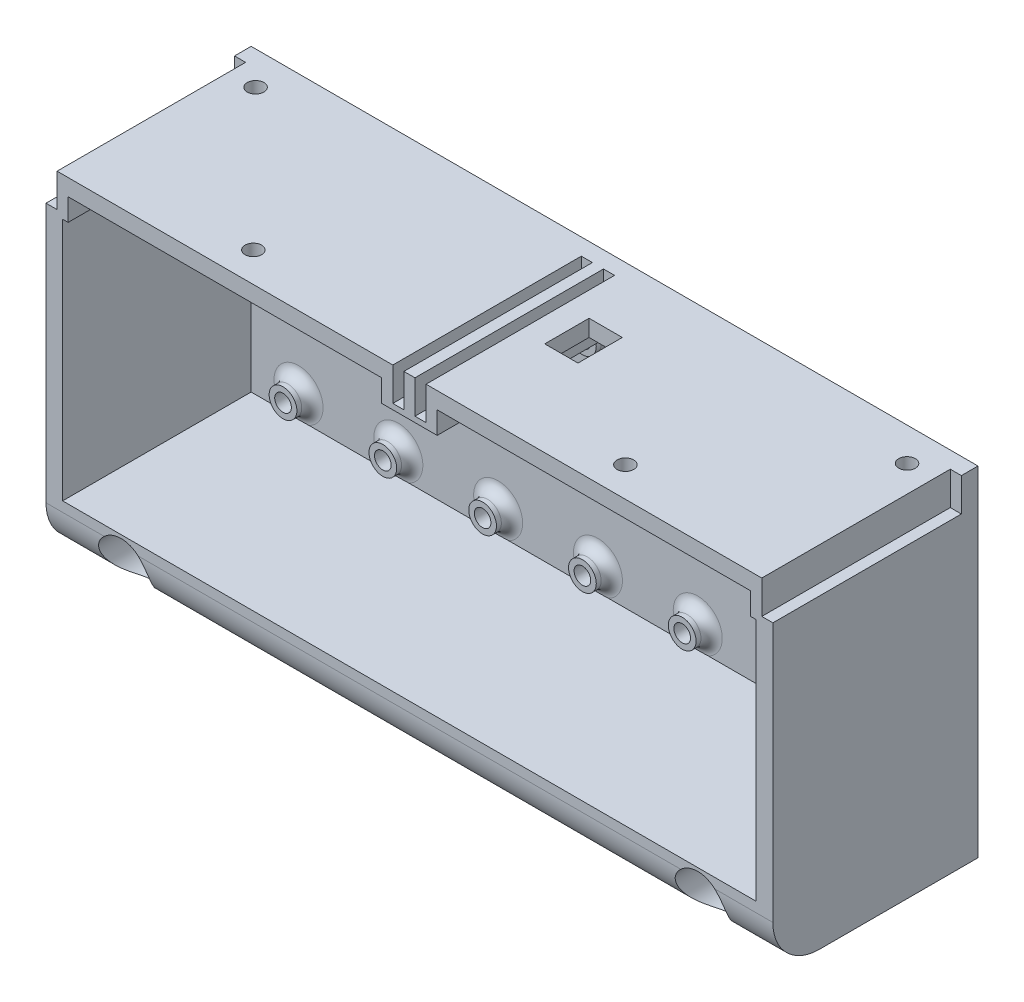
SolidWorks part; units mm, degrees
material "ABS"
ref_plane "Alzado" through (0, 0, 0) normal (0, 0, 1) x (1, 0, 0)
ref_plane "Planta" through (0, 0, 0) normal (0, 1, 0) x (1, 0, 0)
ref_plane "Vista lateral" through (0, 0, 0) normal (1, 0, 0) x (0, 0, -1)
sketch "Croquis2" plane through (0, 0, 0) normal (0, 0, 1) x (1, 0, 0)
  line L0 (0, 0) -> (131.1, 0)
  line L1 (131.1, 0) -> (131.1, -54)
  line L2 (131.1, -54) -> (0, -54)
  line L3 (0, -54) -> (0, 0)
  dimension "D1" = 131.1
  dimension "D2" = 54
extrude "Saliente-Extruir2" add sketch "Croquis2" along normal blind 3
sketch "Croquis3" plane through (0, 0, 3) normal (0, 0, 1) x (1, 0, 0)
  line L0 (0, -6) -> (2, -6)
  line L1 (0, 0) -> (0, -54) construction
  line L2 (2, -6) -> (2, 0)
  line L3 (131.1, 0) -> (0, 0) construction
  line L4 (2, 0) -> (129.1, 0)
  line L5 (129.1, 0) -> (129.1, -6)
  line L6 (129.1, -6) -> (131.1, -6)
  line L7 (131.1, -54) -> (131.1, 0) construction
  line L8 (131.1, -6) -> (131.1, -54)
  line L9 (131.1, -54) -> (0, -54)
  line L10 (0, -54) -> (0, -6)
  line L11 (65.55, 0) -> (66.55, 0)
  line L12 (65.55, 0) -> (64.55, 0)
  line L13 (64.55, 0) -> (64.55, -6)
  line L14 (66.55, 0) -> (66.55, -6)
  line L15 (64.55, -6) -> (62.55, -6)
  line L16 (62.55, -6) -> (62.55, 0)
  line L17 (66.55, -6) -> (68.55, -6)
  line L18 (68.55, -6) -> (68.55, 0)
  line L19 (3, -7) -> (128.1, -7)
  line L20 (128.1, -7) -> (128.1, -51)
  line L21 (128.1, -51) -> (3, -51)
  line L22 (3, -51) -> (3, -7)
  point P31 (130.1, -6)
  line M15 (0, 0) -> (0, -54)
  line M16 (0, -54) -> (131.1, -54)
  line M17 (131.1, -54) -> (131.1, 0)
  line M18 (131.1, 0) -> (0, 0)
  dimension "D1" = 2
  dimension "D2" = 2
  dimension "D3" = 6
  dimension "D4" = 2
  dimension "D5" = 2
  dimension "D6" = 1
  dimension "D7" = 1
  dimension "D8" = 3
  dimension "D9" = 3
  dimension "D10" = 3
  dimension "D11" = 1
extrude "Saliente-Extruir3" add sketch "Croquis3" along normal blind 34 contours L18 L17 L14 L4 L13 L15 L16 L2 L0 L6 L5 L21 L22 L19 L20 M18 M15 M16 M17 region at (1, -7.4179, 3)
sketch "Croquis4" plane through (0, -54, 0) normal (0, -1, 0) x (1, 0, 0)
  line L4 (0, 0) -> (131.1, 0)
  line L5 (131.1, 0) -> (131.1, 37)
  line L6 (131.1, 37) -> (0, 37)
  line L7 (0, 37) -> (0, 0)
  line L8 (0, 0) -> (131.1, 0)
  line L9 (131.1, 0) -> (131.1, 37)
  line L10 (131.1, 37) -> (0, 37)
  line L11 (0, 37) -> (0, 0)
  dimension "D1" = 0
extrude "Saliente-Extruir4" add sketch "Croquis4" along normal blind 7.2
sketch "Croquis5" plane through (0, 0, 37) normal (0, 0, 1) x (1, 0, 0)
  line L0 (3, -7) -> (128.1, -7) construction
  line L1 (4, -7) -> (60.55, -7)
  line L2 (4, -7) -> (4, -3)
  line L3 (4, -3) -> (60.55, -3)
  line L4 (60.55, -7) -> (60.55, -3)
  line L5 (62.55, 0) -> (2, 0) construction
  line L6 (65.55, -7) -> (65.55, 0) construction
  line L7 (66.55, 0) -> (64.55, 0) construction
  line L8 (127.1, -3) -> (70.55, -3)
  line L9 (70.55, -7) -> (70.55, -3)
  line L10 (127.1, -7) -> (70.55, -7)
  line L11 (127.1, -7) -> (127.1, -3)
  dimension "D1" = 1
  dimension "D2" = 2
  dimension "D3" = 3
extrude "Cortar-Extruir1" cut sketch "Croquis5" against normal up to vertex (34 mm away) up to point (3, -7, 3)
sketch "Croquis6" plane through (0, -3, 0) normal (0, -1, 0) x (1, 0, 0)
  line L0 (60.55, 37) -> (4, 37) construction
  line L1 (0, 37) -> (0, 3) construction
  line L2 (131.1, 37) -> (131.1, 3) construction
  line L3 (131.1, 0) -> (0, 0) construction
  line L4 (127.1, 3) -> (70.55, 3) construction
  line L5 (72.95, 20) -> (78.95, 20)
  line L6 (72.95, 20) -> (72.95, 12)
  line L7 (72.95, 12) -> (78.95, 12)
  line L8 (78.95, 20) -> (78.95, 12)
  circle A0 centre (32, 31.6) radius 1.5
  circle A1 centre (99.1, 31.6) radius 1.5
  circle A2 centre (6.8, 6) radius 1.5
  circle A3 centre (124.3, 6) radius 1.5
  point P16 (63.45, 31.6)
  dimension "D3" = 3
  dimension "D1" = 5.4
  dimension "D2" = 32
  dimension "D4" = 32
  dimension "D5" = 6.8
  dimension "D6" = 6
  dimension "D7" = 6.8
  dimension "D8" = 63.45
  dimension "D9" = 4.4
  dimension "D10" = 9
  dimension "D11" = 6
  dimension "D12" = 8
extrude "Cortar-Extruir2" cut sketch "Croquis6" against normal up to next
sketch "Croquis8" plane through (0, 0, 37) normal (0, 0, 1) x (1, 0, 0)
  line L0 (65.55, -61.2) -> (65.55, -51) construction
  line L1 (131.1, -61.2) -> (0, -61.2) construction
  line L2 (128.1, -51) -> (3, -51) construction
  circle A0 centre (13.55, -56.1) radius 4.5
  circle A1 centre (117.55, -56.1) radius 4.5
  point P8 (65.55, -56.1)
  dimension "D1" = 9
  dimension "D2" = 52
extrude "Cortar-Extruir3" cut sketch "Croquis8" against normal blind 33
sketch "Croquis9" plane through (0, 0, 37) normal (0, 0, 1) x (1, 0, 0)
  circle A0 centre (13.55, -56.1) radius 2.5
  circle A1 centre (117.55, -56.1) radius 2.5
  dimension "D1" = 5
extrude "Cortar-Extruir4" cut sketch "Croquis9" against normal through all
fillet "Redondeo1" radius 8.4 1 edges at (65.55, -61.2, 37)
sketch "Croquis10" plane through (0, 0, 3) normal (0, 0, 1) x (1, 0, 0)
  line L0 (60.55, -7) -> (70.55, -7) construction
  line L1 (60.55, -7) -> (70.55, -7) construction
  circle A0 centre (65.55, -10) radius 2.5
  circle A1 centre (65.55, -10) radius 1.5
  circle A2 centre (83.55, -10) radius 1.5
  circle A3 centre (83.55, -10) radius 2.5
  circle A4 centre (101.55, -10) radius 1.5
  circle A5 centre (101.55, -10) radius 2.5
  circle A6 centre (119.55, -10) radius 1.5
  circle A7 centre (119.55, -10) radius 2.5
  circle A8 centre (83.55, -47) radius 1.5
  circle A9 centre (83.55, -47) radius 2.5
  circle A10 centre (101.55, -47) radius 1.5
  circle A11 centre (101.55, -47) radius 2.5
  circle A12 centre (119.55, -47) radius 1.5
  circle A13 centre (119.55, -47) radius 2.5
  circle A16 centre (47.55, -10) radius 2.5
  circle A17 centre (47.55, -10) radius 1.5
  circle A18 centre (29.55, -10) radius 2.5
  circle A19 centre (29.55, -10) radius 1.5
  circle A20 centre (11.55, -10) radius 2.5
  circle A21 centre (11.55, -10) radius 1.5
  circle A22 centre (47.55, -47) radius 2.5
  circle A23 centre (47.55, -47) radius 1.5
  circle A24 centre (29.55, -47) radius 2.5
  circle A25 centre (29.55, -47) radius 1.5
  circle A26 centre (11.55, -47) radius 2.5
  circle A27 centre (11.55, -47) radius 1.5
  circle A28 centre (65.55, -47) radius 2.5
  circle A29 centre (65.55, -47) radius 1.5
  circle A30 centre (65.55, -47) radius 2.5 [skipped]
  circle A31 centre (65.55, -47) radius 1.5 [skipped]
  point P5 (65.55, -7)
  dimension "D1" = 5
  dimension "D3" = 3
  dimension "D2" = 3
  dimension "D4" = 4
  dimension "D5" = 2
  dimension "D6" = 4
  dimension "D7" = 2
extrude "Saliente-Extruir5" add sketch "Croquis10" along normal blind 2.8
fillet "Redondeo2" radius 1.92 14 edges at (9.05, -47, 3) (27.05, -47, 3) (45.05, -47, 3) (63.05, -47, 3) (81.05, -47, 3) (99.05, -47, 3) (117.05, -47, 3) (117.05, -10, 3) (99.05, -10, 3) (81.05, -10, 3) (63.05, -10, 3) (45.05, -10, 3) (27.05, -10, 3) (9.05, -10, 3)
